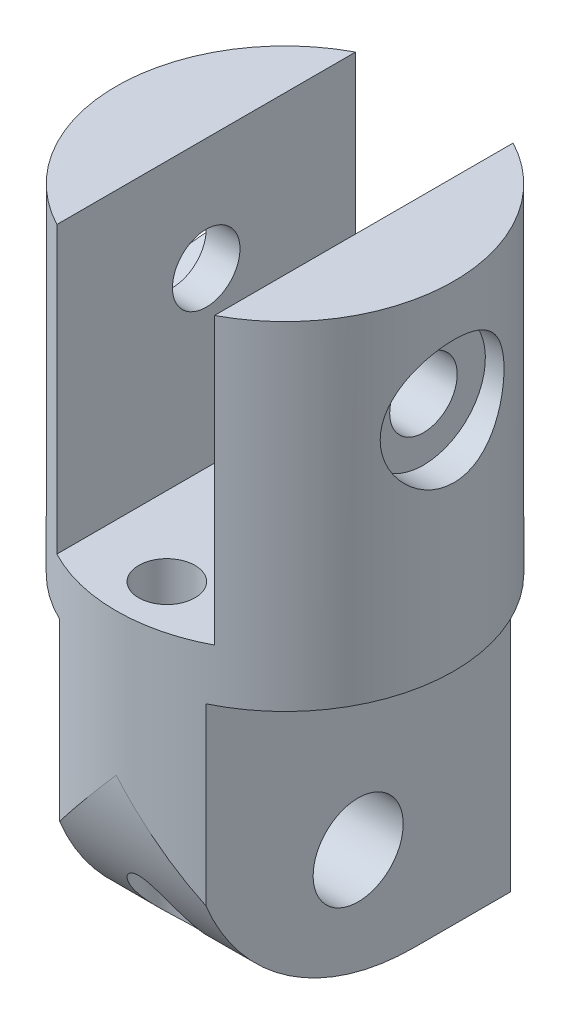
SolidWorks part; units mm, degrees
ref_plane "Front Plane" through (0, 0, 0) normal (0, 0, 1) x (1, 0, 0)
ref_plane "Top Plane" through (0, 0, 0) normal (0, 1, 0) x (1, 0, 0)
ref_plane "Right Plane" through (0, 0, 0) normal (1, 0, 0) x (0, 0, -1)
sketch "Sketch1" plane through (0, 0, 0) normal (0, 0, 1) x (1, 0, 0)
  line L1 (-3.25, 7) -> (3.25, 7)
  line L2 (-3.25, 7) -> (-3.25, -7)
  line L3 (-3.25, -7) -> (3.25, -7)
  line L4 (3.25, 7) -> (3.25, -7)
  line L5 (-3.25, 7) -> (3.25, -7) construction
  line L6 (-3.25, -7) -> (3.25, 7) construction
  point P0 (0, 0)
  dimension "D1" = 6.5
  dimension "D2" = 14
extrude "Boss-Extrude1" add sketch "Sketch1" along normal blind 15
fillet "Fillet1" radius 10 1 edges at (0, -7, 15)
sketch "Sketch2" plane through (3.25, 0, 0) normal (1, 0, 0) x (0, 0, -1)
  line L0 (-7.5, 7) -> (-7.5, -6.6825) construction
  line L1 (-15, 7) -> (0, 7) construction
  arc A0 (-15, 3) -> (-5, -7) centre (-5, 3) ccw construction
  circle A1 centre (-7.5, -2) radius 2
  dimension "D1" = 4
  dimension "D2" = 4.6825
extrude "Cut-Extrude1" cut sketch "Sketch2" against normal through all
sketch "Sketch4" plane through (0, 7, 0) normal (0, 1, 0) x (1, 0, 0)
  line L0 (0, 0) -> (0, -15) construction
  line L1 (3.25, 0) -> (-3.25, 0) construction
  line L2 (3.25, -15) -> (-3.25, -15) construction
  circle A0 centre (0, -7.5) radius 7.5
  dimension "D1" = 15
extrude "Boss-Extrude2" add sketch "Sketch4" along normal blind 15
sketch "Sketch6" plane through (0, 0, 0) normal (0, 0, -1) x (-1, 0, 0)
  line L0 (7.5, 22) -> (-7.5, 22) construction
  line L1 (3.5, 22) -> (-3.5, 22)
  line L2 (3.5, 22) -> (3.5, 9.32)
  line L3 (3.5, 9.32) -> (-3.5, 9.32)
  line L4 (-3.5, 22) -> (-3.5, 9.32)
  point P4 (0, 9.32)
  dimension "D1" = 7
  dimension "D2" = 12.68
extrude "Cut-Extrude2" cut sketch "Sketch6" against normal through all
sketch "Sketch7" plane through (0, 7, 0) normal (0, 1, 0) x (1, 0, 0)
  line L2 (-3.25, -14.2593) -> (-3.25, -15)
  line L3 (-3.25, -15) -> (0, -15)
  line L4 (-3.25, -14.2593) -> (-3.25, -15)
  line L5 (-3.25, -15) -> (0, -15)
  line L6 (0, -15) -> (3.25, -15)
  line L7 (3.25, -15) -> (3.25, -14.2593)
  line L8 (0, -15) -> (3.25, -15)
  line L9 (3.25, -15) -> (3.25, -14.2593)
  line L10 (0, 0) -> (-3.25, 0)
  line L11 (-3.25, 0) -> (-3.25, -0.7407)
  line L12 (0, 0) -> (-3.25, 0)
  line L13 (-3.25, 0) -> (-3.25, -0.7407)
  line L14 (3.25, -0.7407) -> (3.25, 0)
  line L15 (3.25, 0) -> (0, 0)
  line L16 (3.25, -0.7407) -> (3.25, 0)
  line L17 (3.25, 0) -> (0, 0)
  arc A1 (-3.25, -14.2593) -> (0, -15) centre (0, -7.5) ccw
  arc A2 (-3.25, -14.2593) -> (0, -15) centre (0, -7.5) ccw
  arc A3 (0, -15) -> (3.25, -14.2593) centre (0, -7.5) ccw
  arc A4 (0, -15) -> (3.25, -14.2593) centre (0, -7.5) ccw
  arc A5 (0, 0) -> (-3.25, -0.7407) centre (0, -7.5) ccw
  arc A6 (0, 0) -> (-3.25, -0.7407) centre (0, -7.5) ccw
  arc A7 (3.25, -0.7407) -> (0, 0) centre (0, -7.5) ccw
  arc A8 (3.25, -0.7407) -> (0, 0) centre (0, -7.5) ccw
  arc M13 (0, -15) -> (-3.25, -14.2593) centre (0, -7.5) cw
  line M14 (-3.25, -14.2593) -> (-3.25, -15)
  line M15 (-3.25, -15) -> (0, -15)
  dimension "D1" = 0
  dimension "D2" = 0
  dimension "D3" = 0
  dimension "D4" = 0
extrude "Cut-Extrude3" cut sketch "Sketch7" against normal through all contours A6 L12 L13 | A8 L16 L17 | M15 M13 M14 | A4 L8 L9 region at (-2.4457, 7, 14.7798) region at (2.4457, 7, 14.7798) region at (-2.4457, 7, 0.2202) region at (2.4457, 7, 0.2202)
sketch "Sketch8" plane through (-3.5, 0, 0) normal (1, 0, 0) x (0, 0, -1)
  line L0 (-7.5, 9.32) -> (-7.5, 22) construction
  line L1 (-14.1332, 9.32) -> (-0.8668, 9.32) construction
  line L2 (-0.8668, 22) -> (-14.1332, 22) construction
  circle A0 centre (-7.5, 17) radius 1.5
  dimension "D2" = 3
  dimension "D1" = 5
extrude "Cut-Extrude4" cut sketch "Sketch8" against normal mid plane 42
ref_plane "Plane1" through (6.15, 0, 0) normal (-1, 0, 0) x (0, 0, 1)
sketch "Sketch9" plane through (6.15, 0, 0) normal (-1, 0, 0) x (0, 0, 1)
  circle A0 centre (7.5, 17) radius 2.75
  dimension "D1" = 5.5
extrude "Cut-Extrude5" cut sketch "Sketch9" against normal blind 10
ref_plane "Plane2" through (-5, 0, 0) normal (1, 0, 0) x (0, 0, -1)
sketch "Sketch10" plane through (-5, 0, 0) normal (1, 0, 0) x (0, 0, -1)
  line L0 (-7.5, 20.7528) -> (-7.5, 17) construction
  line L1 (-7.5, 20.7528) -> (-10.75, 18.8764)
  line L2 (-10.75, 18.8764) -> (-10.75, 15.1236)
  line L3 (-10.75, 15.1236) -> (-7.5, 13.2472)
  line L4 (-7.5, 13.2472) -> (-4.25, 15.1236)
  line L5 (-4.25, 15.1236) -> (-4.25, 18.8764)
  line L6 (-4.25, 18.8764) -> (-7.5, 20.7528)
  circle A0 centre (-7.5, 17) radius 3.25 construction
  dimension "D1" = 6.5
extrude "Cut-Extrude6" cut sketch "Sketch10" against normal blind 10
sketch "Sketch11" plane through (0, -7, 0) normal (0, -1, 0) x (1, 0, 0)
  line L0 (3.25, 5) -> (-3.25, 5) construction
  circle A1 centre (0, 3) radius 1.25
  circle A3 centre (0, 12.7488) radius 1.25
  dimension "D1" = 2
extrude "Cut-Extrude7" cut sketch "Sketch11" against normal blind 24 contours A3 | A1 region at (0, -7, 3) region at (0, -7, 12.7488)
